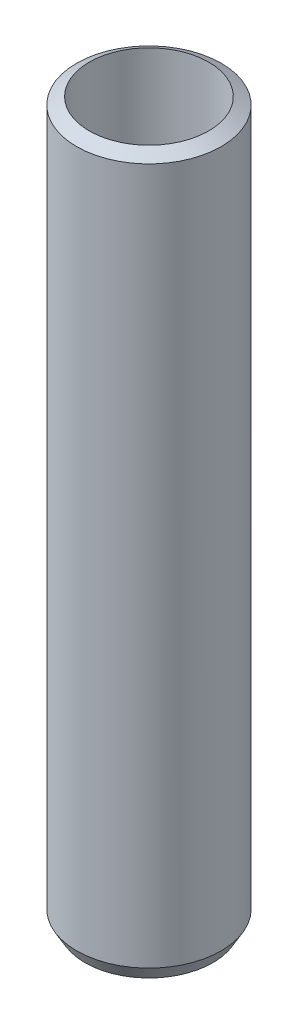
SolidWorks part; units mm, degrees
ref_plane "Front Plane" through (0, 0, 0) normal (0, 0, 1) x (1, 0, 0)
ref_plane "Top Plane" through (0, 0, 0) normal (0, 1, 0) x (1, 0, 0)
ref_plane "Right Plane" through (0, 0, 0) normal (1, 0, 0) x (0, 0, -1)
sketch "Sketch1" plane through (0, 0, 0) normal (0, 1, 0) x (1, 0, 0)
  circle A0 centre (0, 0) radius 40
  dimension "SHAFT_OD" = 80
extrude "Boss-Extrude1" add sketch "Sketch1" along normal blind 398.0886
sketch "Sketch2" plane through (0, 0, 0) normal (0, 1, 0) x (1, 0, 0)
  circle A0 centre (0, 0) radius 33.0332
  dimension "BORE_D" = 66.0664
extrude "Cut-Extrude1" cut sketch "Sketch2" along normal through all
chamfer "Chamfer1" distance 4.6259 angle 60 2 edges at (0, 398.0886, 40) (0, 0, 40) first distance on face at (0, 398.0886, 40) first distance on face at (0, 0, 33.0332)
